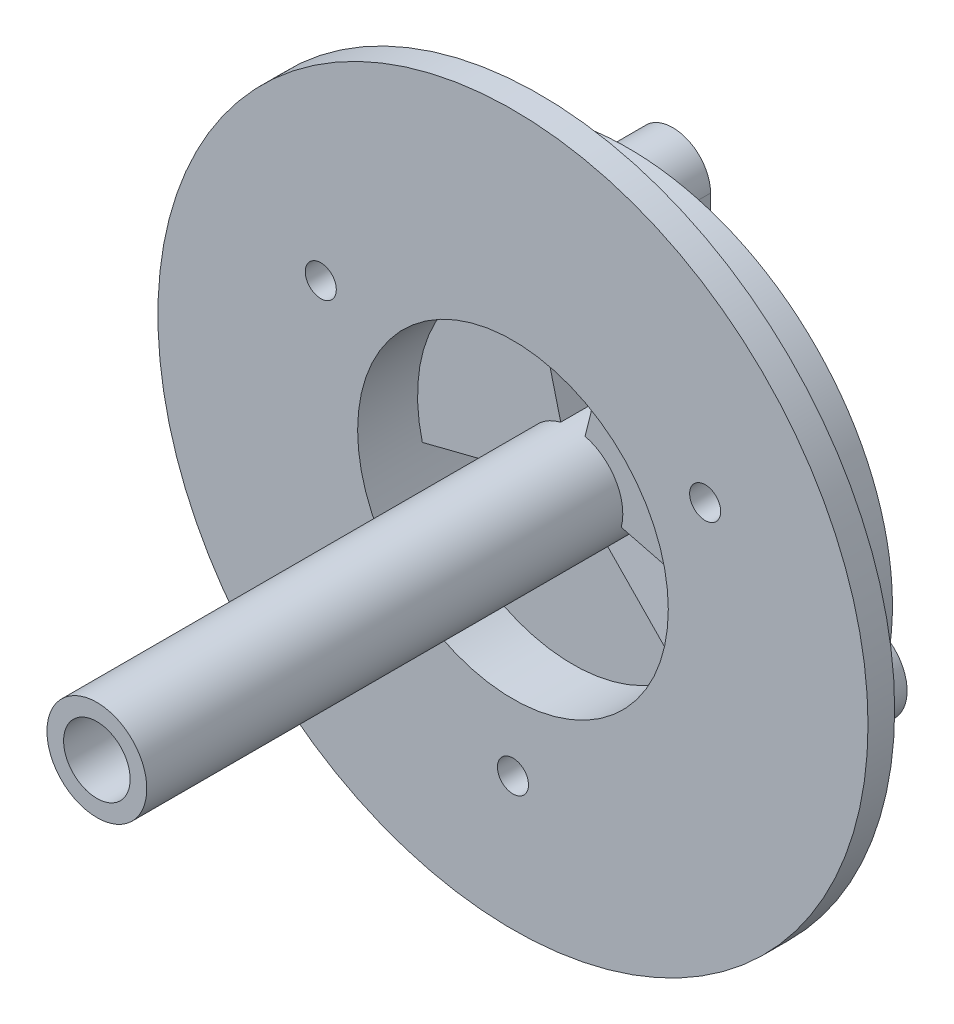
SolidWorks part; units mm, degrees
ref_plane "前视基准面" through (0, 0, 0) normal (0, 0, 1) x (1, 0, 0)
ref_plane "上视基准面" through (0, 0, 0) normal (0, 1, 0) x (1, 0, 0)
ref_plane "右视基准面" through (0, 0, 0) normal (1, 0, 0) x (0, 0, -1)
sketch "草图1" plane through (0, 0, 0) normal (0, 0, 1) x (1, 0, 0)
  circle A0 centre (0, 0) radius 16
extrude "凸台-拉伸1" add sketch "草图1" along normal blind 1.2
sketch "草图2" plane through (0, 0, 1.2) normal (0, 0, 1) x (1, 0, 0)
  circle A0 centre (0, 0) radius 7
extrude "切除-拉伸1" cut sketch "草图2" against normal blind 1.2
sketch "草图3" plane through (0, 0, 1.2) normal (0, 0, 1) x (1, 0, 0)
  circle A2 centre (8.6603, 5) radius 0.7
  circle A3 centre (0, -10) radius 0.7
  circle A4 centre (-8.6603, 5) radius 0.7
extrude "切除-拉伸2" cut sketch "草图3" against normal blind 1.2
sketch "草图4" plane through (0, 0, 0) normal (0, 0, -1) x (-1, 0, 0)
  line L3 (1.7039, 10) -> (1.7039, 5.3952)
  line L16 (-5.5379, -1.0034) -> (-3.6379, -4.2943)
  line L17 (3.6379, -4.2943) -> (5.5379, -1.0034)
  line L18 (1.7039, 5.3952) -> (-1.7039, 5.3952)
  line L19 (-5.5379, -1.0034) -> (-9.6103, -3.3546)
  line L21 (3.6379, -4.2943) -> (7.7103, -6.6454)
  line L25 (-3.6379, -4.2943) -> (-7.7103, -6.6454)
  line L31 (5.5379, -1.0034) -> (9.6103, -3.3546)
  line L32 (-1.7039, 5.3952) -> (-1.7039, 10)
  circle A1 centre (8.6603, -5) radius 0.9
  circle A2 centre (-8.6603, -5) radius 0.9
  circle A3 centre (0, 10) radius 0.9
  arc A4 (1.7039, 10) -> (-1.7039, 10) centre (0, 10) ccw
  arc A5 (7.7103, -6.6454) -> (9.6103, -3.3546) centre (8.6603, -5) ccw
  arc A6 (-9.6103, -3.3546) -> (-7.7103, -6.6454) centre (-8.6603, -5) ccw
extrude "凸台-拉伸2" add sketch "草图4" along normal blind 6
sketch "草图5" plane through (0, 0, 1.2) normal (0, 0, 1) x (1, 0, 0)
  circle A0 centre (0, 0) radius 7
extrude "切除-拉伸3" cut sketch "草图5" against normal blind 11
sketch "草图6" plane through (0, 0, 0) normal (0, 0, -1) x (-1, 0, 0)
  circle A0 centre (0, 0) radius 11.9
  circle A1 centre (0, 0) radius 7
extrude "凸台-拉伸3" add sketch "草图6" along normal blind 4
sketch "草图7" plane through (0, 0, 1.2) normal (0, 0, 1) x (1, 0, 0)
  circle A0 centre (-8.6603, 5) radius 0.7
  circle A1 centre (8.6603, 5) radius 0.7
  circle A2 centre (0, -10) radius 0.7
extrude "切除-拉伸4" cut sketch "草图7" against normal blind 13
sketch "草图8" plane through (0, 0, -4) normal (0, 0, -1) x (-1, 0, 0)
  circle A0 centre (0, 0) radius 2.25
extrude "凸台-拉伸4" add sketch "草图8" against normal blind 33 separate body
sketch "草图9" plane through (0, 0, -4) normal (0, 0, -1) x (-1, 0, 0)
  line L0 (-1.57, -1.6117) -> (-4.8846, -5.0141)
  line L1 (1.57, -1.6117) -> (4.8846, -5.0141)
  line L2 (-2.1808, -0.5539) -> (-6.7846, -1.7232)
  line L3 (-0.5477, 2.1823) -> (-1.7039, 6.7895)
  line L4 (0.5477, 2.1823) -> (1.7039, 6.7895)
  line L5 (2.1808, -0.5539) -> (6.7846, -1.7232)
  arc A0 (-4.8846, -5.0141) -> (4.8846, -5.0141) centre (0, 0) ccw
  arc A1 (-1.7039, 6.7895) -> (-6.7846, -1.7232) centre (0, 0) ccw
  arc A2 (6.7846, -1.7232) -> (1.7039, 6.7895) centre (0, 0) ccw
  arc A3 (2.1808, -0.5539) -> (0.5477, 2.1823) centre (0, 0) ccw
  arc A4 (-1.57, -1.6117) -> (1.57, -1.6117) centre (0, 0) ccw
  arc A5 (-0.5477, 2.1823) -> (-2.1808, -0.5539) centre (0, 0) ccw
extrude "凸台-拉伸5" add sketch "草图9" against normal blind 2.5
sketch "草图10" plane through (0, 0, -4) normal (0, 0, -1) x (-1, 0, 0)
  circle A0 centre (0, 0) radius 1.5
extrude "切除-拉伸5" cut sketch "草图10" against normal blind 33.5
sketch "草图12" plane through (0, 0, 0) normal (1, 0, 0) x (0, 0, -1)
  line L3 (-19.95, -5.0897) -> (-33.7637, -5.0897)
  line L4 (-19.95, -5.0897) -> (-19.95, 5.3715)
  line L5 (-19.95, 5.3715) -> (-33.7637, 5.3715)
  line L6 (-33.7637, -5.0897) -> (-33.7637, 5.3715)
extrude "切除-拉伸6" cut sketch "草图12" against normal mid plane 33.5
